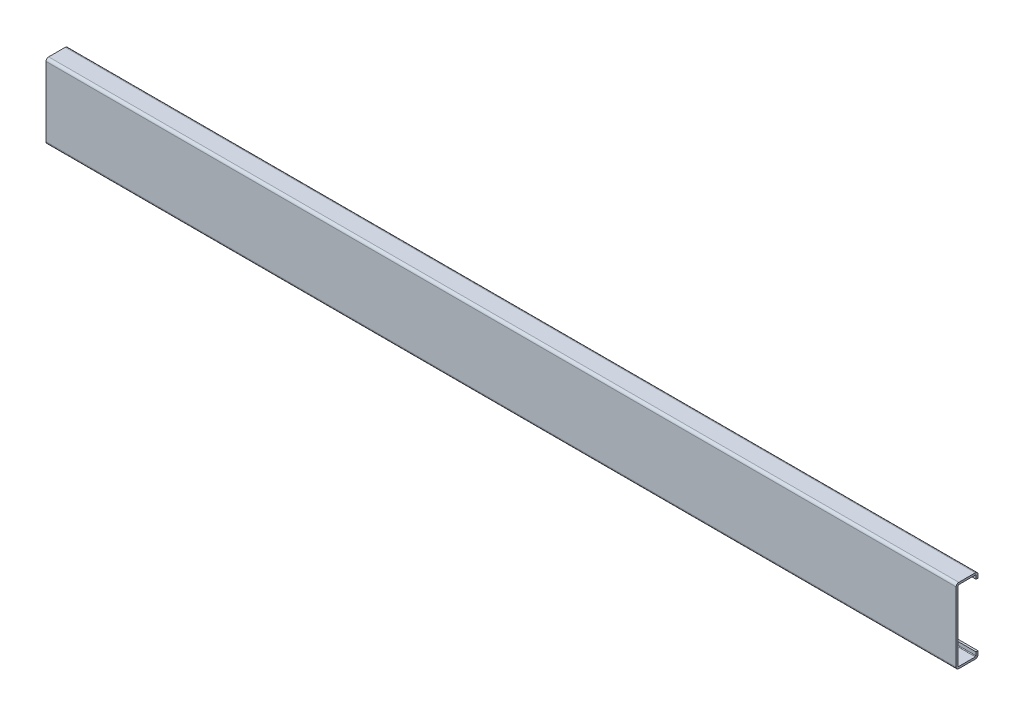
SolidWorks part; units mm, degrees
ref_plane "Спереди" through (0, 0, 0) normal (0, 0, 1) x (1, 0, 0)
ref_plane "Сверху" through (0, 0, 0) normal (0, 1, 0) x (1, 0, 0)
ref_plane "Справа" through (0, 0, 0) normal (1, 0, 0) x (0, 0, -1)
sketch "Эскиз1" plane through (0, 0, 0) normal (1, 0, 0) x (0, 0, -1)
  line L0 (0, -21) -> (0, 21)
  line L1 (-12.4481, 0) -> (26.4522, 0) construction
  line L2 (1, 22) -> (11, 22)
  line L3 (12, 21) -> (12, 19)
  line L4 (12, -21) -> (12, -19)
  line L5 (1, -22) -> (11, -22)
  arc A0 (11, 22) -> (12, 21) centre (11, 21) cw
  arc A1 (0, 21) -> (1, 22) centre (1, 21) cw
  arc A2 (0, -21) -> (1, -22) centre (1, -21) ccw
  arc A3 (11, -22) -> (12, -21) centre (11, -21) ccw
  point P0 (0, 0)
  point P19 (0, 0)
  dimension "D1" = 1
extrude "Вытянуть-Тонкостенный1" add sketch "Эскиз1" along normal blind 550 thin thin type mid plane wall 1.2
